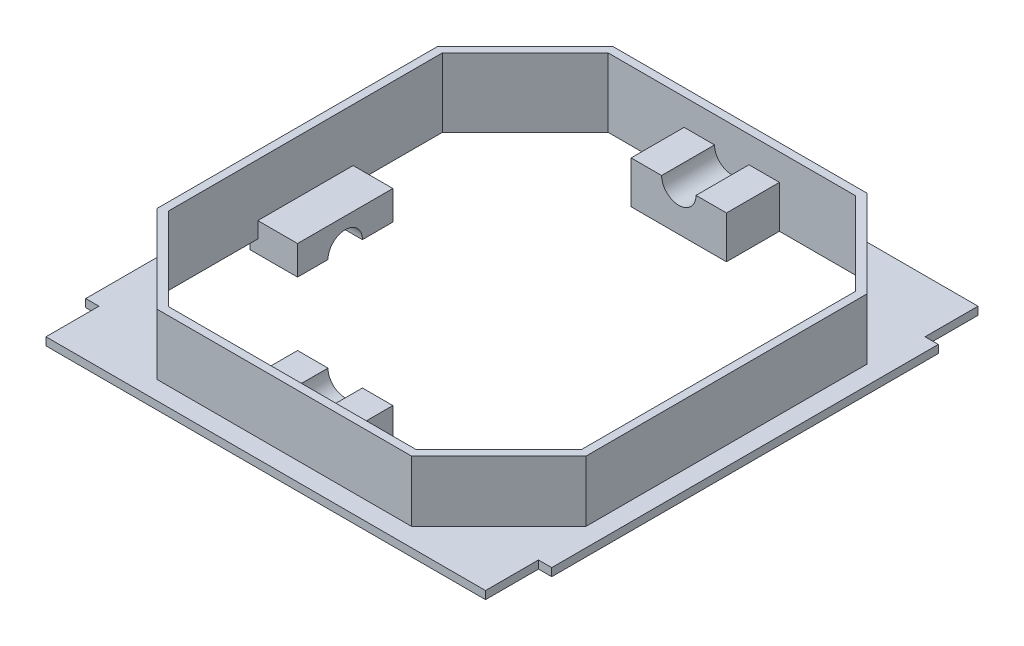
SolidWorks part; units mm, degrees
ref_plane "Front Plane" through (0, 0, 0) normal (0, 0, 1) x (1, 0, 0)
ref_plane "Top Plane" through (0, 0, 0) normal (0, 1, 0) x (1, 0, 0)
ref_plane "Right Plane" through (0, 0, 0) normal (1, 0, 0) x (0, 0, -1)
sketch "Sketch1" plane through (0, 0, 0) normal (0, 1, 0) x (1, 0, 0)
  line L5 (-44, -46.5) -> (44, -46.5)
  line L6 (-44, -46.5) -> (-44, 46.5)
  line L7 (-44, 46.5) -> (44, 46.5)
  line L8 (44, -46.5) -> (44, 46.5)
  line L9 (-44, -46.5) -> (44, 46.5) construction
  line L10 (-44, 46.5) -> (44, -46.5) construction
  point P0 (0, 0)
  dimension "D1" = 88
  dimension "D2" = 93
extrude "Boss-Extrude1" add sketch "Sketch1" along normal blind 13
sketch "Sketch2" plane through (0, 13, 0) normal (0, 1, 0) x (1, 0, 0)
  line L0 (0, 46.5) -> (0, -46.5) construction
  line L1 (-44, -46.5) -> (44, -46.5) construction
  line L2 (-44, 0) -> (44, 0) construction
  line L3 (44, -46.5) -> (44, 46.5) construction
  line L4 (-24, -43) -> (-40.5, -26.5)
  line L5 (-44, 46.5) -> (-44, -46.5) construction
  line L6 (-44, -36.5) -> (-44, -46.5)
  line L7 (-44, -46.5) -> (-34, -46.5)
  line L11 (-24, -43) -> (24, -43)
  line L14 (-34, -46.5) -> (34, -46.5)
  line L15 (-40.5, -26.5) -> (-40.5, 26.5)
  line L17 (-44, -36.5) -> (-44, 36.5)
  line L18 (44, -36.5) -> (44, 36.5)
  line L19 (40.5, -26.5) -> (40.5, 26.5)
  line L20 (44, -46.5) -> (34, -46.5)
  line L21 (44, -36.5) -> (44, -46.5)
  line L22 (24, -43) -> (40.5, -26.5)
  line L23 (24, 43) -> (40.5, 26.5)
  line L24 (44, 36.5) -> (44, 46.5)
  line L25 (44, 46.5) -> (34, 46.5)
  line L26 (-34, 46.5) -> (34, 46.5)
  line L27 (-24, 43) -> (24, 43)
  line L28 (-44, 46.5) -> (-34, 46.5)
  line L29 (-44, 36.5) -> (-44, 46.5)
  line L30 (-24, 43) -> (-40.5, 26.5)
  point P6 (0, 0)
  point P12 (0, 0)
  point P29 (0, -43)
  point P35 (40.5, 0)
  point P37 (-40.5, 0)
  point P40 (0, 43)
  dimension "D1" = 45
  dimension "D2" = 10
  dimension "D3" = 10
  dimension "D4" = 3.5
  dimension "D5" = 3.5
  dimension "D6" = 20
extrude "Cut-Extrude1" cut sketch "Sketch2" against normal offset from surface (11.5 mm away) 1.5 up to face at (0, 0, 0)
sketch "Sketch3" plane through (0, 13, 0) normal (0, 1, 0) x (1, 0, 0)
  line L16 (-23.3787, -41.5) -> (23.3787, -41.5)
  line L17 (23.3787, -41.5) -> (39, -25.8787)
  line L18 (39, -25.8787) -> (39, 25.8787)
  line L19 (39, 25.8787) -> (23.3787, 41.5)
  line L20 (23.3787, 41.5) -> (-23.3787, 41.5)
  line L21 (-23.3787, 41.5) -> (-39, 25.8787)
  line L22 (-39, 25.8787) -> (-39, -25.8787)
  line L23 (-39, -25.8787) -> (-23.3787, -41.5)
  line L24 (-23.3787, -41.5) -> (23.3787, -41.5)
  line L25 (23.3787, -41.5) -> (39, -25.8787)
  line L26 (39, -25.8787) -> (39, 25.8787)
  line L27 (39, 25.8787) -> (23.3787, 41.5)
  line L28 (23.3787, 41.5) -> (-23.3787, 41.5)
  line L29 (-23.3787, 41.5) -> (-39, 25.8787)
  line L30 (-39, 25.8787) -> (-39, -25.8787)
  line L31 (-39, -25.8787) -> (-23.3787, -41.5)
  dimension "D1" = 1.5
extrude "Cut-Extrude2" cut sketch "Sketch3" against normal through all
sketch "Sketch4" plane through (0, 0, -41.5) normal (0, 0, 1) x (1, 0, 0)
  line L0 (0, 0) -> (0, 8) construction
  line L1 (23.3787, 0) -> (-23.3787, 0) construction
  line L2 (3.25, 8) -> (9, 8)
  line L3 (9, 8) -> (9, 0)
  line L4 (-9, 0) -> (9, 0)
  line L5 (3.25, 8) -> (-3.25, 8) construction
  line L6 (-9, 8) -> (-9, 0)
  line L7 (-3.25, 8) -> (-9, 8)
  arc A0 (-3.25, 8) -> (3.25, 8) centre (0, 8) ccw
  point P4 (3.25, 7.0837)
  dimension "D1" = 3.25
  dimension "D2" = 8
  dimension "D3" = 18
extrude "Boss-Extrude2" add sketch "Sketch4" along normal blind 10
sketch "Sketch5" plane through (39, 0, 0) normal (-1, 0, 0) x (0, 0, 1)
  line L0 (0, 0) -> (0, -2.5) construction
  line L2 (25.8787, 0) -> (-25.8787, 0) construction
  line L3 (3.25, -2.5) -> (9, -2.5)
  line L4 (9, -2.5) -> (9, 3)
  line L6 (-9, -2.5) -> (-9, 3)
  line L7 (-3.25, -2.5) -> (-9, -2.5)
  line L8 (-9, 3) -> (9, 3)
  arc A1 (3.25, -2.5) -> (-3.25, -2.5) centre (0, -2.5) ccw
  point P11 (0, 0)
  dimension "D2" = 2.5
  dimension "D1" = 6.5
  dimension "D3" = 18
  dimension "D4" = 5.5
extrude "Boss-Extrude3" add sketch "Sketch5" along normal blind 7.5 and the other way up to surface (1.5 mm away) other way up to face at (40.5, 7.25, 0)
extrude "Boss-Extrude4" add sketch "Sketch5<2>" against normal blind 7.5 and the other way up to surface (79.5 mm away) from surface other way up to face at (-40.5, 7.25, 0) starting at face at (-39, 6.5, 0)
sketch "Sketch5<2>" plane through (39, 0, 0) normal (-1, 0, 0) x (0, 0, 1) same geometry as "Sketch5"
extrude "Boss-Extrude5" add sketch "Sketch4<2>" against normal blind 10 from surface starting at face at (0, 6.5, 41.5)
sketch "Sketch4<2>" plane through (0, 0, -41.5) normal (0, 0, 1) x (1, 0, 0) same geometry as "Sketch4"
sketch "Sketch6" plane through (0, 1.5, 0) normal (0, 1, 0) x (1, 0, 0)
  line L0 (-44, 0) -> (44, 0) construction
  line L1 (44, -46.5) -> (41.5, -46.5)
  line L2 (44, -46.5) -> (44, -36.5)
  line L3 (44, -36.5) -> (41.5, -36.5)
  line L4 (41.5, -46.5) -> (41.5, -36.5)
  line L5 (44, -46.5) -> (44, 46.5) construction
  line L6 (0, -46.5) -> (0, 46.5) construction
  line L7 (44, 46.5) -> (-44, 46.5) construction
  line L8 (41.5, 46.5) -> (41.5, 36.5)
  line L9 (44, 36.5) -> (41.5, 36.5)
  line L10 (44, 46.5) -> (44, 36.5)
  line L11 (44, 46.5) -> (41.5, 46.5)
  line L12 (-44, 46.5) -> (-41.5, 46.5)
  line L13 (-44, 46.5) -> (-44, 36.5)
  line L14 (-44, 36.5) -> (-41.5, 36.5)
  line L15 (-41.5, 46.5) -> (-41.5, 36.5)
  line L16 (-41.5, -46.5) -> (-41.5, -36.5)
  line L17 (-44, -36.5) -> (-41.5, -36.5)
  line L18 (-44, -46.5) -> (-44, -36.5)
  line L19 (-44, -46.5) -> (-41.5, -46.5)
  point P12 (0, 0)
  point P17 (0, 0)
  dimension "D1" = 2.5
  dimension "D2" = 10
extrude "Cut-Extrude3" cut sketch "Sketch6" against normal through all
